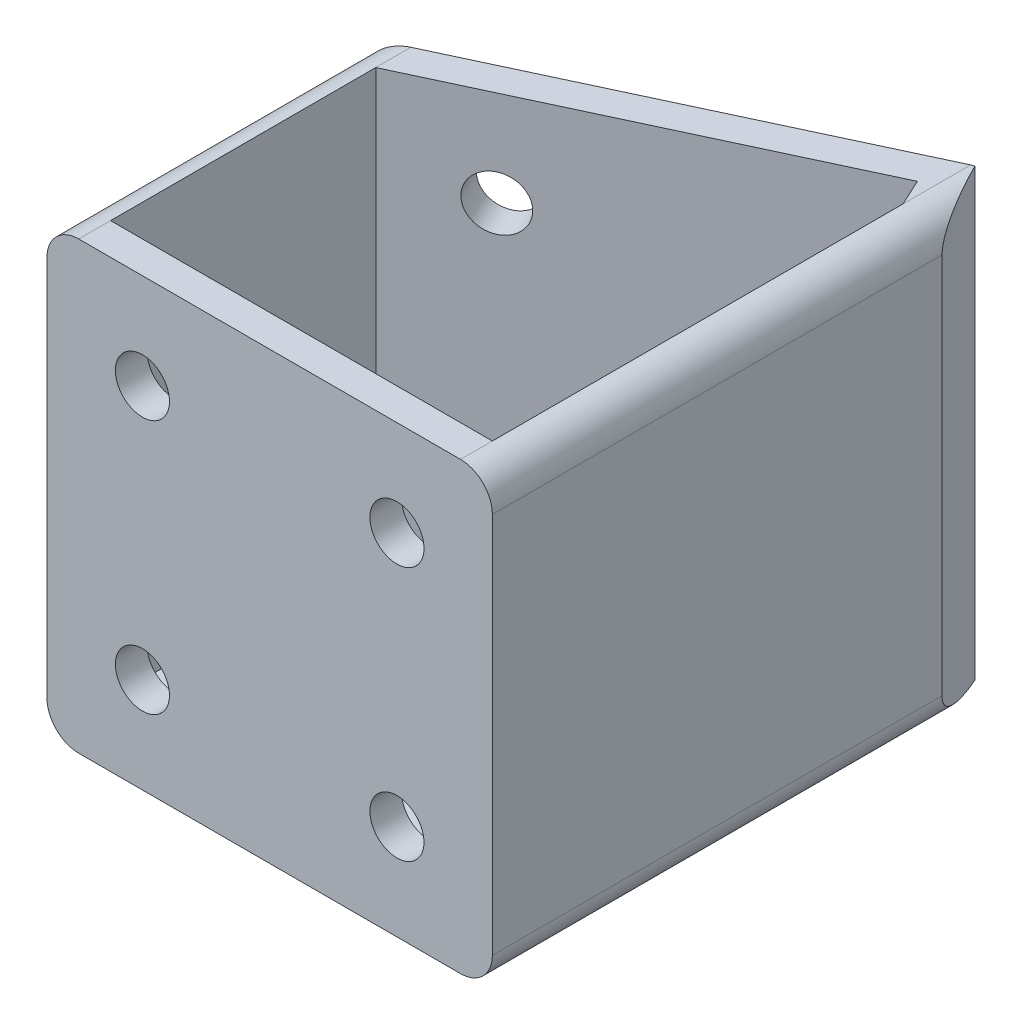
SolidWorks part; units mm, degrees
ref_plane "Front Plane" through (0, 0, 0) normal (0, 0, 1) x (1, 0, 0)
ref_plane "Top Plane" through (0, 0, 0) normal (0, 1, 0) x (1, 0, 0)
ref_plane "Right Plane" through (0, 0, 0) normal (1, 0, 0) x (0, 0, -1)
sketch "Sketch1" plane through (0, 0, 0) normal (0, 0, 1) x (1, 0, 0)
  line L1 (-14, 14) -> (14, 14)
  line L2 (-14, 14) -> (-14, -14)
  line L3 (-14, -14) -> (14, -14)
  line L4 (14, 14) -> (14, -14)
  line L5 (-14, 14) -> (14, -14) construction
  line L6 (-14, -14) -> (14, 14) construction
  point P0 (0, 0)
  dimension "D1" = 28
  dimension "D2" = 28
  dimension "D3" = 28
  dimension "D4" = 28
extrude "Boss-Extrude1" add sketch "Sketch1" along normal blind 33
ref_plane "Plane1" through (2.5005, 0, 5.3623) normal (0.4226, 0, 0.9063) x (0, 1, 0)
sketch "Sketch3" plane through (2.5005, 0, 5.3623) normal (0.4226, 0, 0.9063) x (0, 1, 0)
  line L1 (23.419, 22.9998) -> (-25.7818, 22.9998)
  line L2 (23.419, 22.9998) -> (23.419, -19.1038)
  line L3 (23.419, -19.1038) -> (-25.7818, -19.1038)
  line L4 (-25.7818, 22.9998) -> (-25.7818, -19.1038)
extrude "Cut-Extrude1" cut sketch "Sketch3" against normal blind 15
fillet "Fillet1" radius 2 4 edges at (14, -14, 16.5) (14, 14, 16.5) (-14, 14, 23.0283) (-14, -14, 23.0283)
ref_plane "Plane2" through (2.5005, 0, -5.3623) normal (0.4226, 0, -0.9063) x (0, 1, 0)
sketch "Sketch5" plane through (2.5005, 0, -5.3623) normal (0.4226, 0, -0.9063) x (0, 1, 0)
  line L1 (-17.8997, 21.3692) -> (22.758, 21.3692)
  line L2 (-17.8997, 21.3692) -> (-17.8997, -1.8469)
  line L3 (-17.8997, -1.8469) -> (22.758, -1.8469)
  line L4 (22.758, 21.3692) -> (22.758, -1.8469)
extrude "Cut-Extrude2" [suppressed] cut sketch "Sketch5" against normal blind 3
ref_plane "Plane3" through (11.4995, 0, -5.3623) normal (0.9063, 0, -0.4226) x (0, 1, 0)
sketch "Sketch7" plane through (11.4995, 0, -5.3623) normal (0.9063, 0, -0.4226) x (0, 1, 0)
  line L1 (-17.3586, 14.1969) -> (18.5739, 14.1969)
  line L2 (-17.3586, 14.1969) -> (-17.3586, 0)
  line L3 (-17.3586, 0) -> (18.5739, 0)
  line L4 (18.5739, 14.1969) -> (18.5739, 0)
extrude "Cut-Extrude3" cut sketch "Sketch7" against normal blind 2
shell "Shell1" thickness 2 removed face at (0, 14, 19.7642)
sketch "Sketch8" plane through (0, 0, 33) normal (0, 0, 1) x (1, 0, 0)
  line L0 (0, 20.9591) -> (0, -20.7579) construction
  line L1 (-26.9618, 0) -> (26.8947, 0) construction
  circle A0 centre (-8, 8) radius 1.7
  circle A1 centre (8, 8) radius 1.7
  circle A2 centre (8, -8) radius 1.7
  circle A3 centre (-8, -8) radius 1.7
  point P16 (0, 0)
  dimension "D1" = 3.4
  dimension "D2" = 8
  dimension "D3" = 8
  dimension "D5" = 8
  dimension "D6" = 8
  dimension "D7" = 8
  dimension "D8" = 8
  dimension "D9" = 8
  dimension "D10" = 8
  dimension "D4" = 4
extrude "Cut-Extrude4" cut sketch "Sketch8" against normal blind 2
sketch "Sketch9" plane through (2.5005, 0, 5.3623) normal (-0.4226, 0, -0.9063) x (-0.9063, 0, 0.4226)
  line L0 (-17.2079, 0) -> (33.172, 0) construction
  line L1 (0, -35.1104) -> (0, 38.5336) construction
  line L2 (18.2063, -12) -> (18.2063, 12) construction
  circle A0 centre (11.2063, -8) radius 1.5903
  circle A1 centre (11.2063, 8) radius 1.7
  circle A2 centre (-6.2937, 0) radius 1.7
  dimension "D1" = 3.4
  dimension "D2" = 3.1807
  dimension "D7" = 3.4
  dimension "D3" = 7
  dimension "D4" = 7
  dimension "D5" = 8
  dimension "D6" = 8
  dimension "D8" = 24.5
extrude "Cut-Extrude5" cut sketch "Sketch9" against normal blind 2
